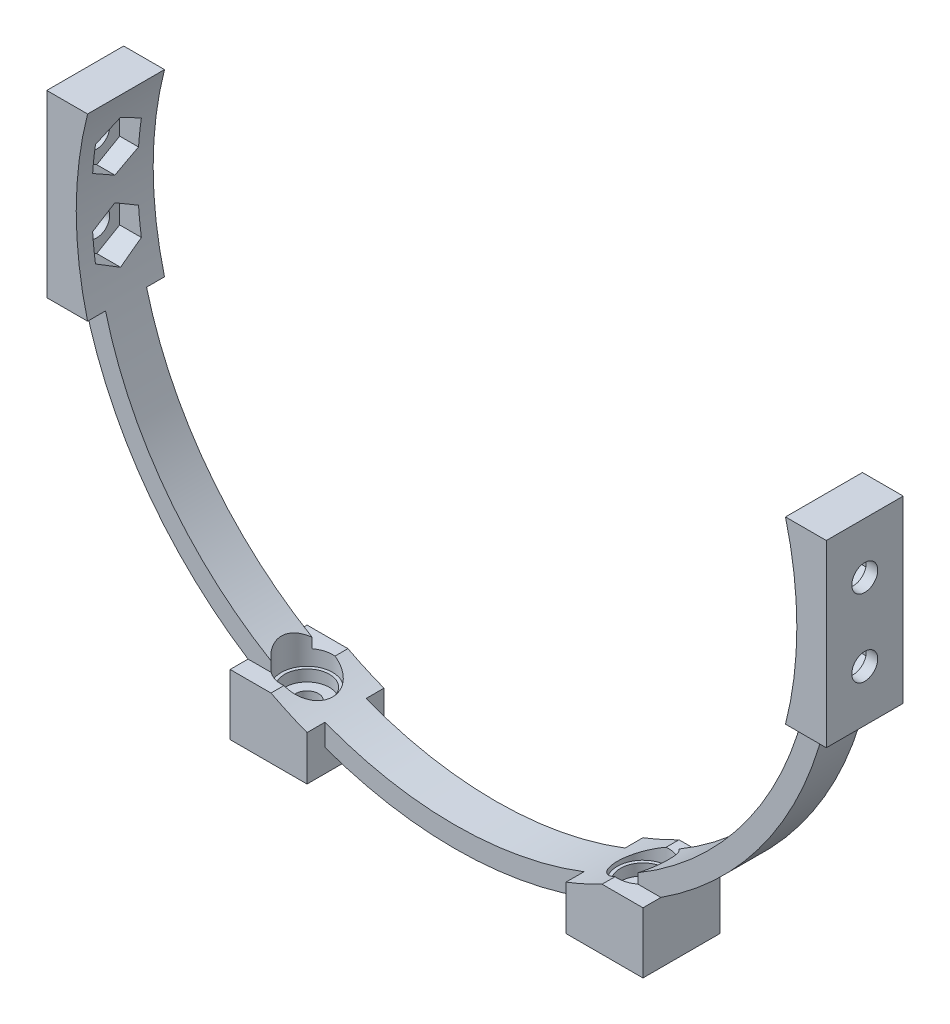
SolidWorks part; units mm, degrees
ref_plane "Front Plane" through (0, 0, 0) normal (0, 0, 1) x (1, 0, 0)
ref_plane "Top Plane" through (0, 0, 0) normal (0, 1, 0) x (1, 0, 0)
ref_plane "Right Plane" through (0, 0, 0) normal (1, 0, 0) x (0, 0, -1)
sketch "Sketch1" plane through (0, 0, 0) normal (0, 0, 1) x (1, 0, 0)
  line L1 (-76, 0) -> (-70.255, 0) construction
  line L2 (-70.255, 0) -> (70.255, 0) construction
  line L3 (76, 0) -> (74.255, 0) construction
  line L5 (-76, 0) -> (-76, -17.5)
  line L6 (-76, 0) -> (-76, 17.5)
  line L7 (-76, 17.5) -> (-70.255, 17.5)
  line L8 (-70.255, 17.5) -> (-70.255, 0) construction
  line L9 (-76, -17.5) -> (-72.1634, -17.5)
  line L11 (0, 0) -> (0, -70.255) construction
  line L12 (70.255, 17.5) -> (70.255, 0) construction
  line L13 (76, 17.5) -> (70.255, 17.5)
  line L14 (76, 0) -> (76, 17.5)
  line L15 (76, 0) -> (76, -17.5)
  line L16 (76, -17.5) -> (72.1634, -17.5)
  line L17 (70.255, 0) -> (76, 0) construction
  line L18 (-70.255, 17.5) -> (-68.0405, 17.5)
  line L19 (-68.0405, 17.5) -> (68.0405, 17.5) construction
  line L20 (68.0405, 17.5) -> (70.255, 17.5)
  line L21 (-72.1634, -17.5) -> (-68.0405, -17.5)
  line L22 (-68.0405, -17.5) -> (68.0405, -17.5) construction
  line L23 (68.0405, -17.5) -> (72.1634, -17.5)
  arc A0 (-70.255, 0) -> (70.255, 0) centre (0, 0) ccw
  arc A1 (-72.1634, -17.5) -> (72.1634, -17.5) centre (0, 0) ccw
  arc A2 (74.255, 0) -> (-74.255, 0) centre (0, 0) ccw construction
  arc A3 (68.0405, 17.5) -> (-68.0405, 17.5) centre (0, 0) ccw construction
  arc A4 (-74.255, 0) -> (-73.7302, -8.8123) centre (0, 0) ccw construction
  arc A5 (-73.7302, -8.8123) -> (-72.1634, -17.5) centre (0, 0) ccw construction
  arc A6 (73.7302, -8.8123) -> (74.255, 0) centre (0, 0) ccw construction
  arc A7 (72.1634, -17.5) -> (73.7302, -8.8123) centre (0, 0) ccw construction
  arc A8 (-68.0405, 17.5) -> (-70.255, 0) centre (0, 0) ccw
  arc A9 (70.255, 0) -> (68.0405, 17.5) centre (0, 0) ccw
  point P12 (-73.1275, 17.5)
  dimension "D1" = 140.51
  dimension "D2" = 4
  dimension "D3" = 76
  dimension "D4" = 35
extrude "Boss-Extrude1" add sketch "Sketch1" along normal mid plane 8 contours A8 L18 L7 L6 L5 L9 L21 A0 | L21 A1 L23 A0 | A9 A0 L23 L16 L15 L14 L13 L20 region at (-72.7273, 0, 0) region at (-70.102, -19.0508, 0) region at (72.7273, 0, 0)
ref_plane "Plane1" through (70.255, 0, 0) normal (-1, 0, 0) x (0, 0, 1)
extrude "Boss-Extrude2" add sketch "Sketch1<5>" along normal mid plane 15 contours A8 L18 L7 L6 L5 L9 L21 A0 | A9 A0 L23 L16 L15 L14 L13 L20 region at (-72.7273, 0, 0) region at (72.7273, 0, 0)
sketch "Sketch1<5>" plane through (0, 0, 0) normal (0, 0, 1) x (1, 0, 0) same geometry as "Sketch1"
sketch "Sketch2" plane through (70.255, 0, 0) normal (-1, 0, 0) x (0, 0, 1)
  line L0 (-7.5, 0) -> (7.5, 0) construction
  line L3 (0, 0) -> (0, 7.5) construction
  line L4 (0, 0) -> (0, -7.5) construction
  line L5 (-7.5, 17.5) -> (-7.5, -17.5) construction
  line L6 (0, 2.3327) -> (4.475, 4.9164)
  line L7 (4.475, 4.9164) -> (4.475, 10.0836)
  line L8 (4.475, 10.0836) -> (0, 12.6673)
  line L9 (0, 12.6673) -> (-4.475, 10.0836)
  line L10 (-4.475, 10.0836) -> (-4.475, 4.9164)
  line L11 (-4.475, 4.9164) -> (0, 2.3327)
  line L12 (0, -12.6673) -> (4.475, -10.0836)
  line L13 (4.475, -10.0836) -> (4.475, -4.9164)
  line L14 (4.475, -4.9164) -> (0, -2.3327)
  line L15 (0, -2.3327) -> (-4.475, -4.9164)
  line L16 (-4.475, -4.9164) -> (-4.475, -10.0836)
  line L17 (-4.475, -10.0836) -> (0, -12.6673)
  line L18 (7.5, -17.5) -> (7.5, 17.5) construction
  circle A0 centre (0, 7.5) radius 4.475 construction
  circle A1 centre (0, -7.5) radius 4.475 construction
  point P5 (0, -7.5)
  point P32 (0, 7.5)
  dimension "D1" = 8.95
  dimension "D2" = 15
extrude "Cut-Extrude1" cut sketch "Sketch2" against normal blind 3.5 and the other way blind 3.5
hole_wizard "#8 (0.199) Diameter Hole1" positions "3DSketch1" profile "Sketch4" hole size "#8" standard "ANSI Inch"
sketch3d "3DSketch1"
  point P0 (76, 7.5, 0)
  point P2 (76, -7.5, 0)
sketch "Sketch4" plane through (76, 7.5, 0) normal (0, 1, 0) x (0, 0, -1)
  line L0 (0, 0) -> (0, 10.71)
  line L1 (0, 10.71) -> (2.5273, 9.1914)
  line L2 (2.5273, 9.1914) -> (2.5273, 0)
  line L5 (2.5273, 0) -> (0, 0)
  line L10 (0, 10.71) -> (-2.5273, 9.1914) construction
  line L11 (0, -6.35) -> (0, 107.95) construction
  dimension "Hole Dia." = 5.0546
  dimension "Hole Depth" = 10.71
  dimension "Drill Angle" = 118
mirror "Mirror1" about plane through (0, 0, 0) normal (1, 0, 0) of "#8 (0.199) Diameter Hole1", "Cut-Extrude1"
sketch "Sketch5" plane through (0, 0, 0) normal (0, 0, 1) x (1, 0, 0)
  line L0 (-40.25, -62.3999) -> (40.25, -62.3999) construction
  line L1 (40.25, -62.3999) -> (40.25, -74.255)
  line L2 (40.25, -74.255) -> (25.25, -74.255)
  line L3 (-25.25, -74.255) -> (-40.25, -74.255)
  line L4 (-40.25, -74.255) -> (-40.25, -62.3999)
  line L5 (-40.25, -65.5607) -> (-25.25, -65.5607) construction
  line L6 (-25.25, -65.5607) -> (-25.25, -74.255)
  line L7 (-40.25, -62.3999) -> (-32.2804, -62.3999)
  line L8 (25.25, -74.255) -> (25.25, -65.5607)
  line L9 (40.25, -62.3999) -> (32.2804, -62.3999)
  line L10 (0, -74.255) -> (-25.25, -74.255) construction
  line L11 (25.25, -74.255) -> (0, -74.255) construction
  arc A0 (-72.1634, -17.5) -> (72.1634, -17.5) centre (0, 0) ccw construction
  arc A1 (-68.0405, -17.5) -> (68.0405, -17.5) centre (0, 0) ccw construction
  arc A2 (-32.2804, -62.3999) -> (-25.25, -65.5607) centre (0, 0) ccw
  arc A3 (-68.0405, -17.5) -> (-32.2804, -62.3999) centre (0, 0) ccw construction
  arc A4 (25.25, -65.5607) -> (32.2804, -62.3999) centre (0, 0) ccw
  arc A5 (-25.25, -65.5607) -> (25.25, -65.5607) centre (0, 0) ccw construction
  arc A6 (32.2804, -62.3999) -> (68.0405, -17.5) centre (0, 0) ccw construction
  dimension "D1" = 80.5
  dimension "D2" = 15
extrude "Boss-Extrude3" add sketch "Sketch5" along normal up to surface and the other way up to surface up to face at (-72.5739, 0, 7.5) other way up to face at (-72.5739, 0, -7.5)
sketch "Sketch6" plane through (0, -62.3999, 0) normal (0, 1, 0) x (1, 0, 0)
  line L0 (-40.25, -7.5) -> (-40.25, 7.5) construction
  line L1 (40.25, 7.5) -> (40.25, -7.5) construction
  line L2 (-25.25, 7.5) -> (-25.25, -7.5) construction
  line L3 (-25.25, -7.5) -> (25.25, -7.5) construction
  line L4 (25.25, -7.5) -> (25.25, 7.5) construction
  line L5 (-40.25, 0) -> (-25.25, 0) construction
  line L6 (25.25, 0) -> (40.25, 0) construction
  circle A0 centre (-32.75, 0) radius 5
  circle A1 centre (32.75, 0) radius 5
  dimension "D1" = 10
extrude "Cut-Extrude2" cut sketch "Sketch6" against normal blind 3 and the other way blind 3.5
hole_wizard "CBORE for #8 Button Head Cap Screw1" positions "3DSketch2" profile "Sketch7" counterbore size "#8" standard "ANSI Inch"
sketch3d "3DSketch2"
  circle A0 centre (32.75, -65.3999, 0) radius 5 construction
  circle A1 centre (-32.75, -65.3999, 0) radius 5 construction
  point P14 (-32.75, -65.3999, 0)
  point P16 (32.75, -65.3999, 0)
  point P19 (0, 0, 0)
  point P22 (32.75, -60.3999, 0)
  point P23 (0, 0, 0)
  point P26 (-32.75, -60.3999, 0)
sketch "Sketch7" plane through (-32.75, -65.3999, 0) normal (1, 0, 0) x (0, 0, 1)
  line L0 (0, 0) -> (0, 13)
  line L1 (0, 13) -> (2.2479, 11.6493)
  line L2 (2.2479, 11.6493) -> (2.2479, 2.2098)
  line L3 (2.2479, 2.2098) -> (4.3663, 2.2098)
  line L4 (4.3663, 2.2098) -> (4.3663, 0)
  line L5 (4.3663, 0) -> (0, 0)
  line L10 (0, 13) -> (-2.2479, 11.6493) construction
  line L11 (0, -6.35) -> (0, 107.95) construction
  dimension "Hole Dia." = 4.4958
  dimension "Hole Depth" = 13
  dimension "C'Bore Dia." = 8.7325
  dimension "C'Bore Depth" = 2.2098
  dimension "Drill Angle" = 118
